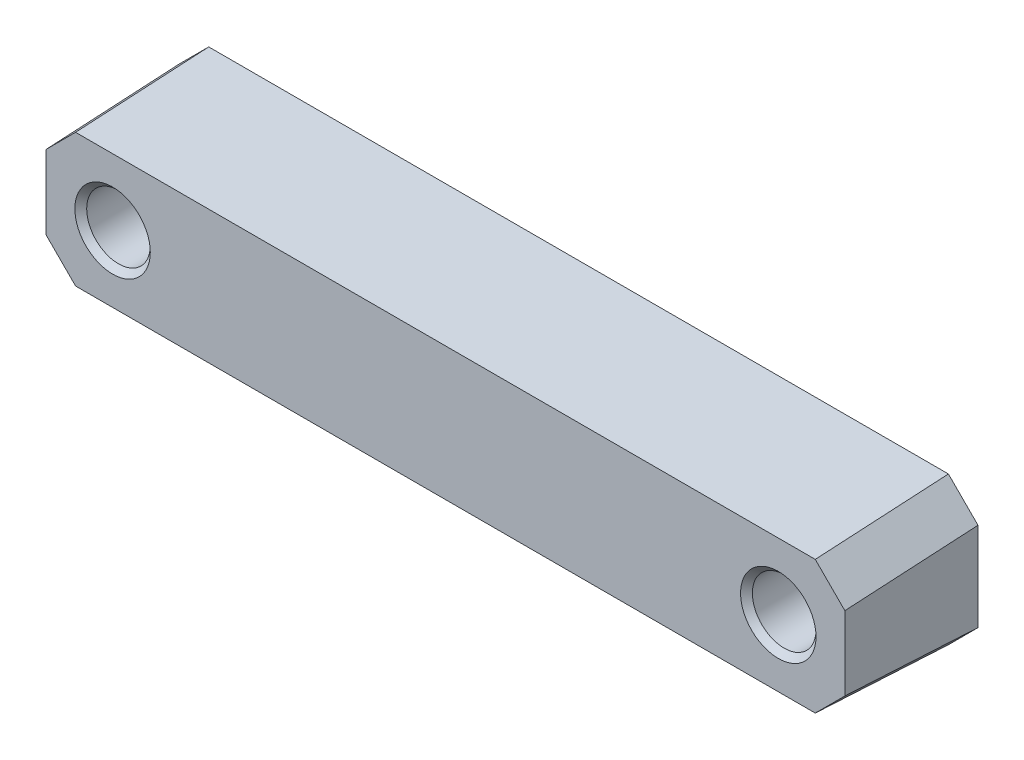
SolidWorks part; units mm, degrees
ref_plane "Front" through (0, 0, 0) normal (0, 0, 1) x (1, 0, 0)
ref_plane "Top" through (0, 0, 0) normal (0, 1, 0) x (1, 0, 0)
ref_plane "Right" through (0, 0, 0) normal (1, 0, 0) x (0, 0, -1)
sketch "Sketch1" plane through (0, 0, 0) normal (0, 0, 1) x (1, 0, 0)
  line L1 (0, 0) -> (54, 0)
  line L2 (0, 0) -> (0, 10)
  line L3 (0, 10) -> (54, 10)
  line L4 (54, 0) -> (54, 10)
  dimension "D1" = 10
  dimension "D2" = 54
ref_plane "Plane1" through (0, 0, 9) normal (0, 0, 1) x (1, 0, 0)
sketch "Sketch2" plane through (0, 0, 9) normal (0, 0, 1) x (1, 0, 0)
  line L0 (0, 0) -> (54, 0) construction
  line L1 (0, 9.5) -> (54, 9.5)
  line L2 (0, 9.5) -> (0, 0.5)
  line L3 (0, 0.5) -> (54, 0.5)
  line L4 (54, 9.5) -> (54, 0.5)
  line L5 (0, 0) -> (0, 10) construction
  dimension "D1" = 54
  dimension "D2" = 9
  dimension "D3" = 0.5
loft "Loft1" add profiles "Sketch1", "Sketch2" connector at (54, 10, 0) connector at (54, 9.5, 9)
sketch "Sketch3" plane through (0, 0, 0) normal (0, 0, -1) x (-1, 0, 0)
  line L0 (0, 0) -> (-54, 0) construction
  line L1 (-54, 0) -> (-54, 10) construction
  circle A0 centre (-49.5, 5) radius 2.15
  circle A1 centre (-4.5, 5) radius 2.15
  dimension "D4" = 4.3
  dimension "D1" = 5
  dimension "D2" = 4.5
  dimension "D3" = 45
extrude "Cut-Extrude1" cut sketch "Sketch3" against normal blind 10
chamfer "Chamfer1" distance 0.4 angle 45 4 edges at (2.35, 5, 0) (6.65, 5, 9) (47.35, 5, 0) (51.65, 5, 9)
chamfer "Chamfer2" distance 2 angle 45 2 edges
chamfer "Chamfer3" distance 2 angle 45 2 edges
